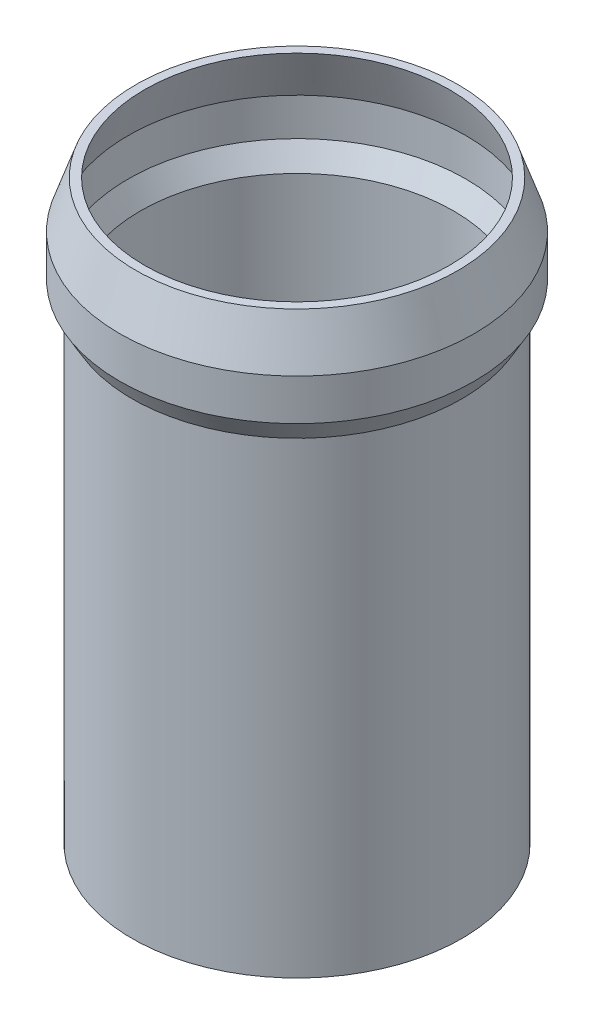
SolidWorks part; units mm, degrees
ref_plane "Front Plane" through (0, 0, 0) normal (0, 0, 1) x (1, 0, 0)
ref_plane "Top Plane" through (0, 0, 0) normal (0, 1, 0) x (1, 0, 0)
ref_plane "Right Plane" through (0, 0, 0) normal (1, 0, 0) x (0, 0, -1)
sketch "Sketch1" plane through (0, 0, 0) normal (0, 0, 1) x (1, 0, 0)
  line L0 (20, 0) -> (20, 56.7271)
  line L1 (20, 56.7271) -> (21.5, 59.3252)
  line L2 (21.5, 59.3252) -> (21.5, 64.3252)
  line L3 (21.5, 64.3252) -> (19.5473, 69.9985)
  line L4 (20, 0) -> (19, 0)
  line L5 (19, 0) -> (19, 1.15)
  line L6 (4.5, 1.15) -> (19, 1.15)
  line L7 (0, 2.4) -> (0, 83.9789) construction
  line L8 (4.5, 2.4) -> (0, 2.4)
  line L9 (4.5, 2.4) -> (4.5, 1.15)
  line L11 (19.5473, 69.9985) -> (0, 69.9985)
  line L12 (0, 69.9985) -> (0, 2.4)
  point P12 (0, 0)
  point P14 (0, 0)
  dimension "D1" = 20
  dimension "D2" = 1
  dimension "D3" = 4.5
  dimension "D4" = 70
  dimension "D5" = 5
  dimension "D6" = 1.5
  dimension "D7" = 3
  dimension "D8" = 6
  dimension "D9" = 1.15
  dimension "D10" = 1.25
revolve "Revolve1" add sketch "Sketch1" angle 360 about L7
fillet "Fillet1" radius 1.5 1 edges at (0, 1.15, -4.5) profile chamfer
shell "Shell1" thickness 1 removed face at (0, 69.9985, -19.5473)
